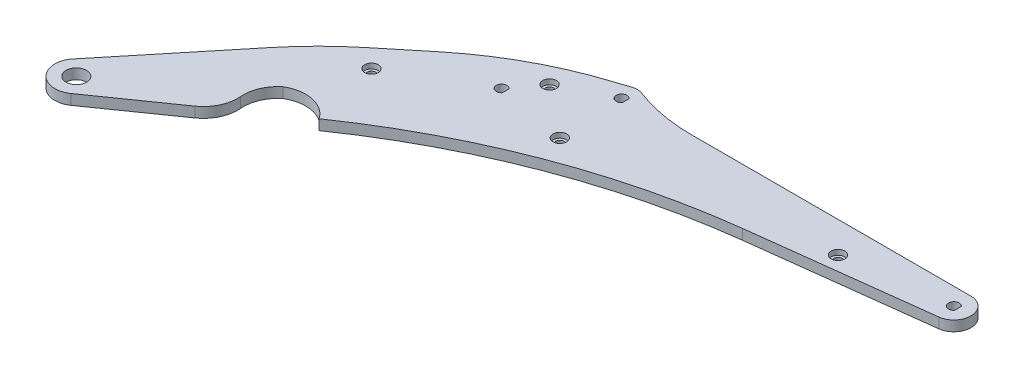
SolidWorks part; units mm, degrees
ref_plane "前视基准面" through (0, 0, 0) normal (0, 0, 1) x (1, 0, 0)
ref_plane "上视基准面" through (0, 0, 0) normal (0, 1, 0) x (1, 0, 0)
ref_plane "右视基准面" through (0, 0, 0) normal (1, 0, 0) x (0, 0, -1)
other "Configuration Table"
sketch "草图3" plane through (0, 0, 0) normal (0, 1, 0) x (1, 0, 0)
  line L0 (0, 0) -> (100, 0)
  line L1 (-82.5612, -80.1259) -> (0, -22.316)
  line L2 (-90.5752, -70.5752) -> (-141.151, -121.151) construction
  line L3 (100.6093, -9.9627) -> (0, -22.316)
  line L4 (-141.151, -121.151) -> (-82.5612, -80.1259) construction
  line L5 (100, 0) -> (181.7493, 0) construction
  line L6 (181.7493, 0) -> (100.6093, -9.9627) construction
  line L7 (101.2, -4.0189) -> (101.2, -5.9811)
  line L8 (-19.8, -15.0189) -> (-19.8, -16.9811)
  line L9 (0.2, -0.0189) -> (0.2, -1.9811)
  line L10 (-20, 0) -> (-90.5752, -70.5752)
  line L11 (-53.0717, -59.4772) -> (-58.8074, -51.2857)
  line L12 (0, 0) -> (-20, 0)
  line L13 (-58.8074, -51.2857) -> (-45.701, -42.1085)
  line L14 (-45.701, -42.1085) -> (-39.9652, -50.3)
  line L16 (-90.5752, -70.5752) -> (-58.8231, -31.7521)
  line L17 (-58.8231, -31.7521) -> (-20, 0)
  circle A0 centre (100, -5) radius 1.55
  circle A1 centre (100, -5) radius 5
  circle A2 centre (-86.1504, -75) radius 6.2576
  circle A3 centre (-1, -1) radius 1.55
  circle A4 centre (-1, -1) radius 4.55
  circle A5 centre (-21, -16) radius 1.55
  circle A6 centre (-86.1504, -75) radius 3
  point P29 (-62.558, -27.3147)
  dimension "D2" = 10
  dimension "D3" = 3.1
  dimension "D10" = 75
  dimension "D11" = 3.1
  dimension "D12" = 3
  dimension "D13" = 3.1
  dimension "D16" = 6
  dimension "D1" = 100
  dimension "D4" = 7
  dimension "D5" = 135
  dimension "D6" = 20
  dimension "D7" = 10
  dimension "D8" = 1
  dimension "D9" = 1
  dimension "D14" = 15
  dimension "D15" = 20
  dimension "D17" = 1.2
  dimension "D18" = 1.2
  dimension "D19" = 1.2
  dimension "D20" = 10
  dimension "D21" = 16
  dimension "D22" = 36
  dimension "D23" = 5
extrude "凸台-拉伸1" add sketch "草图3" along normal blind 3 contours A4 L12 L10 A2 L1 L3 A1 L0 A5 | A2 A6 | L8 A5 | L0 A4 L12 A3 | L9 A3 | L12 A4 L0 A3 | A1 A0 | L7 A0 | L17 L16 L10 region at (-1, 0, -1.5321) region at (-1, 0, 2.6387) region at (-3.2868, 0, 23.095) region at (0.3414, 0, 1) region at (103.4355, 0, 1.5645) region at (-56.4661, 0, 34.1091) region at (-83.8234, 0, 69.3822) region at (101.3414, 0, 5) region at (-19.6586, 0, 16)
fillet "圆角1" radius 200 1 edges at (0, 1.5, 22.316)
fillet "圆角3" radius 50 2 edges at (3.4387, 1.5, 0) (-5.4387, 1.5, 0)
sketch "草图4" plane through (0, 3, 0) normal (0, 1, 0) x (1, 0, 0)
  circle A0 centre (70.2, -9) radius 2
  circle A1 centre (70.2, -9) radius 1.25
  circle A2 centre (0, -20) radius 2
  circle A3 centre (0, -20) radius 1.25
  circle A8 centre (-45, -30) radius 2
  circle A9 centre (-45, -30) radius 1.25
  circle A10 centre (-15, -8) radius 2
  circle A11 centre (-15, -8) radius 1.25
  dimension "D1" = 4
  dimension "D2" = 2.5
  dimension "D3" = 70
  dimension "D4" = 9
  dimension "D5" = 20
  dimension "D6" = 15
  dimension "D7" = 8
  dimension "D8" = 45
  dimension "D9" = 30
extrude "切除-拉伸1" cut sketch "草图4" against normal through all contours A1 | A3 | A11 | A9
extrude "切除-拉伸2" cut sketch "草图4<3>" against normal offset from surface (1.5 mm away) 1.5 contours A0 | A2 | A8 | A10 up to face at (70.2, 0, 10.25)
sketch "草图4<3>" plane through (0, 3, 0) normal (0, 1, 0) x (1, 0, 0) same geometry as "草图4"
fillet "圆角4" radius 10 1 edges at (-53.0717, 1.5, 59.4772)
fillet "圆角5" radius 10 2 edges at (-45.701, 1.5, 42.1085) (-58.8074, 1.5, 51.2857)
fillet "圆角6" radius 100 2 edges at (-20, 1.5, 0) (-58.8231, 1.5, 31.7521)
